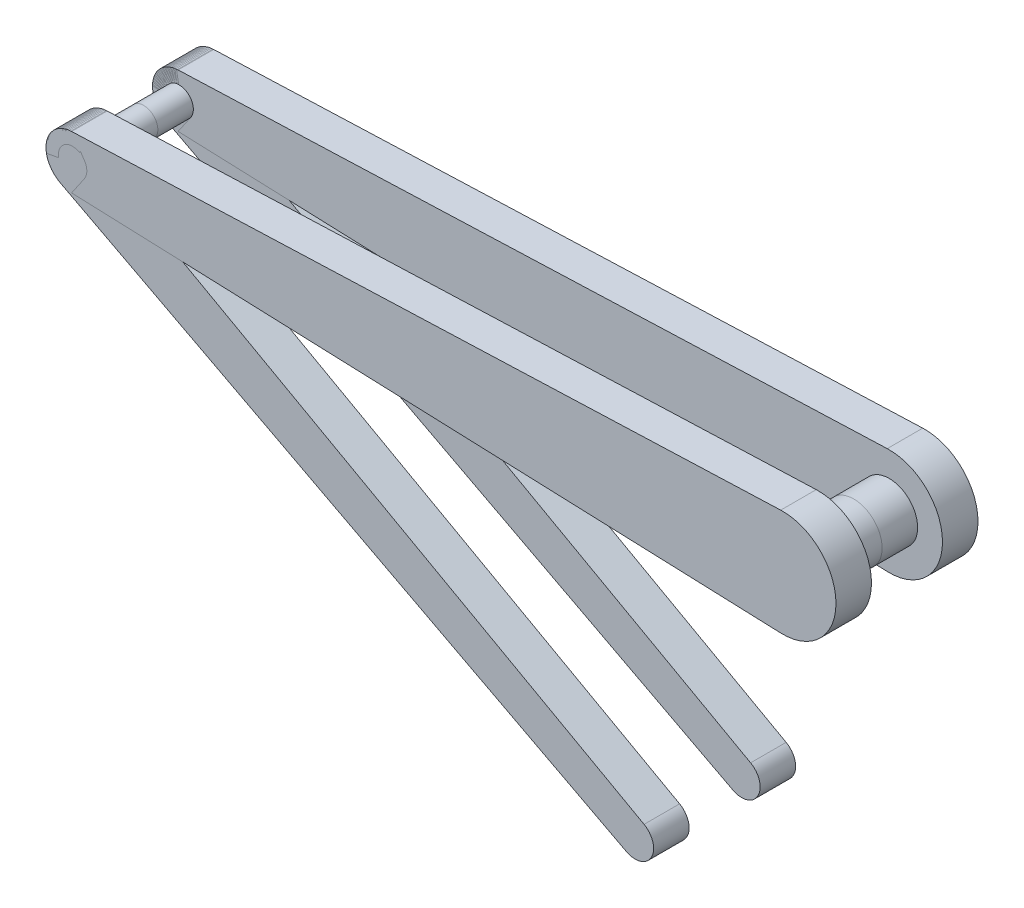
SolidWorks part; units mm, degrees
note: The reader was unsure of these and kept them because the rebuilt part matched: shared geometry of "Sketch1<3>".
ref_plane "Front Plane" through (0, 0, 0) normal (0, 0, 1) x (1, 0, 0)
ref_plane "Top Plane" through (0, 0, 0) normal (0, 1, 0) x (1, 0, 0)
ref_plane "Right Plane" through (0, 0, 0) normal (1, 0, 0) x (0, 0, -1)
sketch "Sketch1" plane through (0, 0, 0) normal (0, 0, 1) x (1, 0, 0)
  line L0 (0, 0) -> (-200, 0) construction
  line L1 (-200.2813, 7.4947) -> (-0.5625, 14.9894)
  line L2 (-200.2813, -7.4947) -> (-0.5625, -14.9894)
  line L3 (-200, 0) -> (-41.5711, -85.4416) construction
  line L4 (-196.356, 6.5552) -> (-39.0431, -80.894)
  line L5 (-203.4755, -6.6461) -> (-43.9822, -90.0522)
  circle A0 centre (0, 0) radius 15
  circle A1 centre (-200, 0) radius 7.5
  circle A2 centre (-41.5711, -85.4416) radius 5.203
  dimension "D1" = 30
  dimension "D2" = 15
  dimension "D4" = 180
  dimension "D3" = 200
  dimension "D5" = 28.338
extrude "Boss-Extrude1" add sketch "Sketch1" along normal blind 10 contours A1 L4 L2 A0 L1 | A0 | A1 | A1 L2 L4
extrude "Boss-Extrude2" add sketch "Sketch1<3>" along normal blind 10 separate body contours A2 L4 L2 A1 L5 | A1 | A1 L2 L4 | A2
sketch "Sketch1<3>" plane through (0, 0, 0) normal (0, 0, 1) x (1, 0, 0) same geometry as "Sketch1"
sketch "Sketch2" plane through (0, 0, 0) normal (0, 0, -1) x (-1, 0, 0)
  circle A0 centre (0, 0) radius 8
extrude "Boss-Extrude3" add sketch "Sketch2" along normal blind 10
sketch "Sketch3" plane through (0, 0, 0) normal (0, 0, -1) x (-1, 0, 0)
  circle A0 centre (200, 0) radius 4
extrude "Boss-Extrude4" add sketch "Sketch3" along normal blind 10
sketch "Sketch4" plane through (0, 0, -10) normal (0, 0, -1) x (-1, 0, 0)
  circle A1 centre (200, 0) radius 4
  circle A2 centre (200, 0) radius 4
  dimension "D1" = 0
extrude "Cut-Extrude1" cut sketch "Sketch4" against normal blind 70
mirror "Mirror1" about plane through (0, 0, -10) normal (0, 0, -1) of bodies 104 105
other "Save Bodies1"
